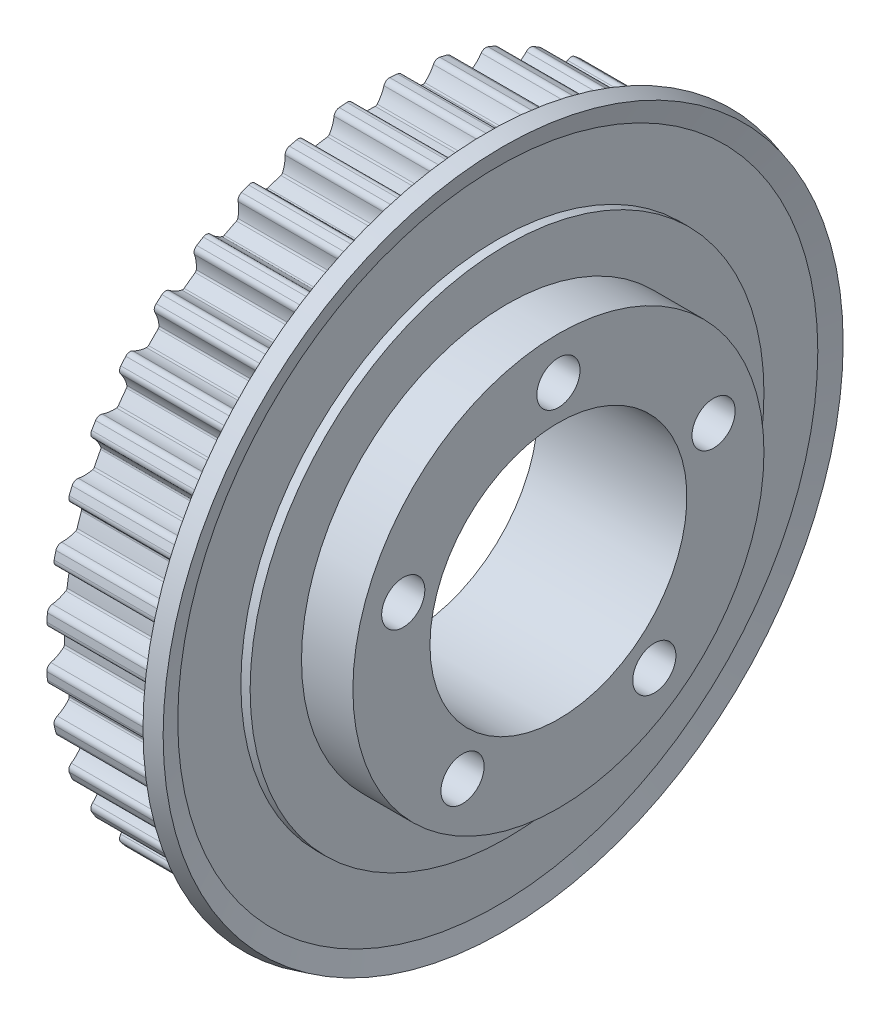
SolidWorks part; units mm, degrees
ref_plane "Front Plane" through (0, 0, 0) normal (0, 0, 1) x (1, 0, 0)
ref_plane "Top Plane" through (0, 0, 0) normal (0, 1, 0) x (1, 0, 0)
ref_plane "Right Plane" through (0, 0, 0) normal (1, 0, 0) x (0, 0, -1)
ref_plane "Plane1" through (0, 0, 0) normal (0, 0, 1) x (1, 0, 0)
sketch "Sketch1" plane through (0, 0, 0) normal (0, 0, 1) x (1, 0, 0)
  line L0 (0, 0) -> (0, 25)
  line L1 (0, 25) -> (0.9, 25)
  line L2 (0.9, 25) -> (0.9, 31.1394)
  line L3 (0.9, 31.1394) -> (0.3784, 33.0859)
  line L4 (0.3784, 33.0859) -> (1.9239, 33.5)
  line L5 (1.9239, 33.5) -> (2.5, 31.35)
  line L6 (2.5, 31.35) -> (13.5, 31.35)
  line L7 (13.5, 31.35) -> (14.0761, 33.5)
  line L8 (14.0761, 33.5) -> (15.6216, 33.0859)
  line L9 (15.6216, 33.0859) -> (15.1, 31.1394)
  line L10 (15.1, 31.1394) -> (15.1, 25)
  line L11 (15.1, 25) -> (16, 25)
  line L12 (16, 25) -> (16, 23.5)
  line L13 (16, 23.5) -> (21, 23.5)
  line L14 (21, 23.5) -> (21, 0)
  line L15 (21, 0) -> (0, 0)
  line L16 (21, 0) -> (0, 0) construction
revolve "Revolve1" add sketch "Sketch1" angle 360 about L16 reverse direction yes
ref_plane "Plane2" through (0, 0, 0) normal (0, 0, 1) x (1, 0, 0)
sketch "Sketch2" plane through (0, 0, 0) normal (0, 0, 1) x (1, 0, 0)
  line L0 (0, 0) -> (0, 12.5)
  line L1 (0, 12.5) -> (21, 12.5)
  line L2 (21, 12.5) -> (21, 0)
  line L3 (21, 0) -> (0, 0)
  line L4 (21, 0) -> (0, 0) construction
revolve "Cut-Revolve1" cut sketch "Sketch2" angle 360 about L4 reverse direction yes
ref_plane "Plane3" through (2.5, 0, 0) normal (1, 0, 0) x (0, 0, -1)
sketch "Sketch3" plane through (2.5, 0, 0) normal (1, 0, 0) x (0, 0, -1)
  line L0 (2.0877, 31.2804) -> (2.0877, 31.7615)
  line L1 (-2.0877, 31.7615) -> (-2.0877, 31.2804)
  arc A0 (-2.0877, 31.2804) -> (-1.5225, 30.8836) centre (-2.0511, 30.7316) cw
  arc A1 (-1.5225, 30.8836) -> (-0.8639, 29.6599) centre (1.625, 31.7885) ccw
  arc A2 (-0.8639, 29.6599) -> (-0.6683, 29.5725) centre (-0.6739, 29.8224) ccw
  arc A3 (-0.6683, 29.5725) -> (0.6683, 29.5725) centre (0, 0) cw
  arc A4 (0.6683, 29.5725) -> (0.8639, 29.6599) centre (0.6739, 29.8224) ccw
  arc A5 (0.8639, 29.6599) -> (1.5225, 30.8836) centre (-1.625, 31.7885) ccw
  arc A6 (1.5225, 30.8836) -> (2.0877, 31.2804) centre (2.0511, 30.7316) cw
  arc A7 (2.0877, 31.7615) -> (-2.0877, 31.7615) centre (0, 0) ccw
extrude "Cut-Extrude1" cut sketch "Sketch3" along normal blind 11
ref_plane "Plane4" through (2.5, 0, 0) normal (1, 0, 0) x (0, 0, -1)
sketch "Sketch4" plane through (2.5, 0, 0) normal (1, 0, 0) x (0, 0, -1)
  line L0 (6.9554, 30.5687) -> (7.0306, 31.0438)
  line L1 (2.9066, 31.697) -> (2.8313, 31.2219)
  arc A0 (2.8313, 31.2219) -> (3.3275, 30.7415) centre (2.7816, 30.6741) cw
  arc A1 (3.3275, 30.7415) -> (3.7865, 29.4299) centre (6.5778, 31.1429) ccw
  arc A2 (3.7865, 29.4299) -> (3.9661, 29.3129) centre (3.9996, 29.5606) ccw
  arc A3 (3.9661, 29.3129) -> (5.2862, 29.1038) centre (0, 0) cw
  arc A4 (5.2862, 29.1038) -> (5.4931, 29.1596) centre (5.3309, 29.3498) ccw
  arc A5 (5.4931, 29.1596) -> (6.335, 30.2652) centre (3.3678, 31.6513) ccw
  arc A6 (6.335, 30.2652) -> (6.9554, 30.5687) centre (6.8333, 30.0324) cw
  arc A7 (7.0306, 31.0438) -> (2.9066, 31.697) centre (0, 0) ccw
extrude "Cut-Extrude2" cut sketch "Sketch4" along normal blind 11
ref_plane "Plane5" through (2.5, 0, 0) normal (1, 0, 0) x (0, 0, -1)
sketch "Sketch5" plane through (2.5, 0, 0) normal (1, 0, 0) x (0, 0, -1)
  line L0 (11.6517, 29.1043) -> (11.8004, 29.5618)
  line L1 (7.8293, 30.8521) -> (7.6806, 30.3946)
  arc A0 (7.6806, 30.3946) -> (8.0956, 29.8425) centre (7.5459, 29.8613) cw
  arc A1 (8.0956, 29.8425) -> (8.3438, 28.4752) centre (11.3687, 29.7305) ccw
  arc A2 (8.3438, 28.4752) -> (8.5028, 28.3316) centre (8.5747, 28.571) ccw
  arc A3 (8.5028, 28.3316) -> (9.774, 27.9186) centre (0, 0) cw
  arc A4 (9.774, 27.9186) -> (9.987, 27.9413) centre (9.8566, 28.1545) ccw
  arc A5 (9.987, 27.9413) -> (10.9915, 28.9016) centre (8.2777, 30.7348) ccw
  arc A6 (10.9915, 28.9016) -> (11.6517, 29.1043) centre (11.4473, 28.5937) cw
  arc A7 (11.8004, 29.5618) -> (7.8293, 30.8521) centre (0, 0) ccw
extrude "Cut-Extrude3" cut sketch "Sketch5" along normal blind 11
ref_plane "Plane6" through (2.5, 0, 0) normal (1, 0, 0) x (0, 0, -1)
sketch "Sketch6" plane through (2.5, 0, 0) normal (1, 0, 0) x (0, 0, -1)
  line L0 (16.0612, 26.9232) -> (16.2796, 27.3519)
  line L1 (12.5592, 29.2475) -> (12.3408, 28.8189)
  arc A0 (12.3408, 28.8189) -> (12.6643, 28.2087) centre (12.1243, 28.3133) cw
  arc A1 (12.6643, 28.2087) -> (12.6956, 26.8194) centre (15.8796, 27.586) ccw
  arc A2 (12.6956, 26.8194) -> (12.8302, 26.6526) centre (12.9386, 26.8779) ccw
  arc A3 (12.8302, 26.6526) -> (14.021, 26.0459) centre (0, 0) cw
  arc A4 (14.021, 26.0459) -> (14.2351, 26.035) centre (14.1396, 26.266) ccw
  arc A5 (14.2351, 26.035) -> (15.3774, 26.8263) centre (12.9838, 29.0615) ccw
  arc A6 (15.3774, 26.8263) -> (16.0612, 26.9232) centre (15.7794, 26.4509) cw
  arc A7 (16.2796, 27.3519) -> (12.5592, 29.2475) centre (0, 0) ccw
extrude "Cut-Extrude4" cut sketch "Sketch6" along normal blind 11
ref_plane "Plane7" through (2.5, 0, 0) normal (1, 0, 0) x (0, 0, -1)
sketch "Sketch7" plane through (2.5, 0, 0) normal (1, 0, 0) x (0, 0, -1)
  line L0 (20.0752, 24.0793) -> (20.3579, 24.4684)
  line L1 (16.9799, 26.9227) -> (16.6972, 26.5335)
  arc A0 (16.6972, 26.5335) -> (16.9212, 25.8803) centre (16.4042, 26.068) cw
  arc A1 (16.9212, 25.8803) -> (16.7347, 24.5032) centre (19.9995, 24.7623) ccw
  arc A2 (16.7347, 24.5032) -> (16.8416, 24.3174) centre (16.9839, 24.5229) ccw
  arc A3 (16.8416, 24.3174) -> (17.9229, 23.5318) centre (0, 0) cw
  arc A4 (17.9229, 23.5318) -> (18.1326, 23.4876) centre (18.0744, 23.7307) ccw
  arc A5 (18.1326, 23.4876) -> (19.3847, 24.0904) centre (17.3702, 26.6726) ccw
  arc A6 (19.3847, 24.0904) -> (20.0752, 24.0793) centre (19.723, 23.6568) cw
  arc A7 (20.3579, 24.4684) -> (16.9799, 26.9227) centre (0, 0) ccw
extrude "Cut-Extrude5" cut sketch "Sketch7" along normal blind 11
ref_plane "Plane8" through (2.5, 0, 0) normal (1, 0, 0) x (0, 0, -1)
sketch "Sketch8" plane through (2.5, 0, 0) normal (1, 0, 0) x (0, 0, -1)
  line L0 (23.5948, 20.6423) -> (23.935, 20.9825)
  line L1 (20.9825, 23.935) -> (20.6423, 23.5948)
  arc A0 (20.6423, 23.5948) -> (20.7614, 22.9146) centre (20.2802, 23.1809) cw
  arc A1 (20.7614, 22.9146) -> (20.3618, 21.5836) centre (23.6269, 21.3288) ccw
  arc A2 (20.3618, 21.5836) -> (20.4383, 21.3834) centre (20.6111, 21.5641) ccw
  arc A3 (20.4383, 21.3834) -> (21.3834, 20.4383) centre (0, 0) cw
  arc A4 (21.3834, 20.4383) -> (21.5836, 20.3618) centre (21.5641, 20.6111) ccw
  arc A5 (21.5836, 20.3618) -> (22.9146, 20.7614) centre (21.3288, 23.6269) ccw
  arc A6 (22.9146, 20.7614) -> (23.5948, 20.6423) centre (23.1809, 20.2802) cw
  arc A7 (23.935, 20.9825) -> (20.9825, 23.935) centre (0, 0) ccw
extrude "Cut-Extrude6" cut sketch "Sketch8" along normal blind 11
ref_plane "Plane9" through (2.5, 0, 0) normal (1, 0, 0) x (0, 0, -1)
sketch "Sketch9" plane through (2.5, 0, 0) normal (1, 0, 0) x (0, 0, -1)
  line L0 (26.5335, 16.6972) -> (26.9227, 16.9799)
  line L1 (24.4684, 20.3579) -> (24.0793, 20.0752)
  arc A0 (24.0793, 20.0752) -> (24.0904, 19.3847) centre (23.6568, 19.723) cw
  arc A1 (24.0904, 19.3847) -> (23.4876, 18.1326) centre (26.6726, 17.3702) ccw
  arc A2 (23.4876, 18.1326) -> (23.5318, 17.9229) centre (23.7307, 18.0744) ccw
  arc A3 (23.5318, 17.9229) -> (24.3174, 16.8416) centre (0, 0) cw
  arc A4 (24.3174, 16.8416) -> (24.5032, 16.7347) centre (24.5229, 16.9839) ccw
  arc A5 (24.5032, 16.7347) -> (25.8803, 16.9212) centre (24.7623, 19.9995) ccw
  arc A6 (25.8803, 16.9212) -> (26.5335, 16.6972) centre (26.068, 16.4042) cw
  arc A7 (26.9227, 16.9799) -> (24.4684, 20.3579) centre (0, 0) ccw
extrude "Cut-Extrude7" cut sketch "Sketch9" along normal blind 11
ref_plane "Plane10" through (2.5, 0, 0) normal (1, 0, 0) x (0, 0, -1)
sketch "Sketch10" plane through (2.5, 0, 0) normal (1, 0, 0) x (0, 0, -1)
  line L0 (28.8189, 12.3408) -> (29.2475, 12.5592)
  line L1 (27.3519, 16.2796) -> (26.9232, 16.0612)
  arc A0 (26.9232, 16.0612) -> (26.8263, 15.3774) centre (26.4509, 15.7794) cw
  arc A1 (26.8263, 15.3774) -> (26.035, 14.2351) centre (29.0615, 12.9838) ccw
  arc A2 (26.035, 14.2351) -> (26.0459, 14.021) centre (26.266, 14.1396) ccw
  arc A3 (26.0459, 14.021) -> (26.6526, 12.8302) centre (0, 0) cw
  arc A4 (26.6526, 12.8302) -> (26.8194, 12.6956) centre (26.8779, 12.9386) ccw
  arc A5 (26.8194, 12.6956) -> (28.2087, 12.6643) centre (27.586, 15.8796) ccw
  arc A6 (28.2087, 12.6643) -> (28.8189, 12.3408) centre (28.3133, 12.1243) cw
  arc A7 (29.2475, 12.5592) -> (27.3519, 16.2796) centre (0, 0) ccw
extrude "Cut-Extrude8" cut sketch "Sketch10" along normal blind 11
ref_plane "Plane11" through (2.5, 0, 0) normal (1, 0, 0) x (0, 0, -1)
sketch "Sketch11" plane through (2.5, 0, 0) normal (1, 0, 0) x (0, 0, -1)
  line L0 (30.3946, 7.6806) -> (30.8521, 7.8293)
  line L1 (29.5618, 11.8004) -> (29.1043, 11.6517)
  arc A0 (29.1043, 11.6517) -> (28.9016, 10.9915) centre (28.5937, 11.4473) cw
  arc A1 (28.9016, 10.9915) -> (27.9413, 9.987) centre (30.7348, 8.2777) ccw
  arc A2 (27.9413, 9.987) -> (27.9186, 9.774) centre (28.1545, 9.8566) ccw
  arc A3 (27.9186, 9.774) -> (28.3316, 8.5028) centre (0, 0) cw
  arc A4 (28.3316, 8.5028) -> (28.4752, 8.3438) centre (28.571, 8.5747) ccw
  arc A5 (28.4752, 8.3438) -> (29.8425, 8.0956) centre (29.7305, 11.3687) ccw
  arc A6 (29.8425, 8.0956) -> (30.3946, 7.6806) centre (29.8613, 7.5459) cw
  arc A7 (30.8521, 7.8293) -> (29.5618, 11.8004) centre (0, 0) ccw
extrude "Cut-Extrude9" cut sketch "Sketch11" along normal blind 11
ref_plane "Plane12" through (2.5, 0, 0) normal (1, 0, 0) x (0, 0, -1)
sketch "Sketch12" plane through (2.5, 0, 0) normal (1, 0, 0) x (0, 0, -1)
  line L0 (31.2219, 2.8313) -> (31.697, 2.9066)
  line L1 (31.0438, 7.0306) -> (30.5687, 6.9554)
  arc A0 (30.5687, 6.9554) -> (30.2652, 6.335) centre (30.0324, 6.8333) cw
  arc A1 (30.2652, 6.335) -> (29.1596, 5.4931) centre (31.6513, 3.3678) ccw
  arc A2 (29.1596, 5.4931) -> (29.1038, 5.2862) centre (29.3498, 5.3309) ccw
  arc A3 (29.1038, 5.2862) -> (29.3129, 3.9661) centre (0, 0) cw
  arc A4 (29.3129, 3.9661) -> (29.4299, 3.7865) centre (29.5606, 3.9996) ccw
  arc A5 (29.4299, 3.7865) -> (30.7415, 3.3275) centre (31.1429, 6.5778) ccw
  arc A6 (30.7415, 3.3275) -> (31.2219, 2.8313) centre (30.6741, 2.7816) cw
  arc A7 (31.697, 2.9066) -> (31.0438, 7.0306) centre (0, 0) ccw
extrude "Cut-Extrude10" cut sketch "Sketch12" along normal blind 11
ref_plane "Plane13" through (2.5, 0, 0) normal (1, 0, 0) x (0, 0, -1)
sketch "Sketch13" plane through (2.5, 0, 0) normal (1, 0, 0) x (0, 0, -1)
  line L0 (31.2804, -2.0877) -> (31.7615, -2.0877)
  line L1 (31.7615, 2.0877) -> (31.2804, 2.0877)
  arc A0 (31.2804, 2.0877) -> (30.8836, 1.5225) centre (30.7316, 2.0511) cw
  arc A1 (30.8836, 1.5225) -> (29.6599, 0.8639) centre (31.7885, -1.625) ccw
  arc A2 (29.6599, 0.8639) -> (29.5725, 0.6683) centre (29.8224, 0.6739) ccw
  arc A3 (29.5725, 0.6683) -> (29.5725, -0.6683) centre (0, 0) cw
  arc A4 (29.5725, -0.6683) -> (29.6599, -0.8639) centre (29.8224, -0.6739) ccw
  arc A5 (29.6599, -0.8639) -> (30.8836, -1.5225) centre (31.7885, 1.625) ccw
  arc A6 (30.8836, -1.5225) -> (31.2804, -2.0877) centre (30.7316, -2.0511) cw
  arc A7 (31.7615, -2.0877) -> (31.7615, 2.0877) centre (0, 0) ccw
extrude "Cut-Extrude11" cut sketch "Sketch13" along normal blind 11
ref_plane "Plane14" through (2.5, 0, 0) normal (1, 0, 0) x (0, 0, -1)
sketch "Sketch14" plane through (2.5, 0, 0) normal (1, 0, 0) x (0, 0, -1)
  line L0 (30.5687, -6.9554) -> (31.0438, -7.0306)
  line L1 (31.697, -2.9066) -> (31.2219, -2.8313)
  arc A0 (31.2219, -2.8313) -> (30.7415, -3.3275) centre (30.6741, -2.7816) cw
  arc A1 (30.7415, -3.3275) -> (29.4299, -3.7865) centre (31.1429, -6.5778) ccw
  arc A2 (29.4299, -3.7865) -> (29.3129, -3.9661) centre (29.5606, -3.9996) ccw
  arc A3 (29.3129, -3.9661) -> (29.1038, -5.2862) centre (0, 0) cw
  arc A4 (29.1038, -5.2862) -> (29.1596, -5.4931) centre (29.3498, -5.3309) ccw
  arc A5 (29.1596, -5.4931) -> (30.2652, -6.335) centre (31.6513, -3.3678) ccw
  arc A6 (30.2652, -6.335) -> (30.5687, -6.9554) centre (30.0324, -6.8333) cw
  arc A7 (31.0438, -7.0306) -> (31.697, -2.9066) centre (0, 0) ccw
extrude "Cut-Extrude12" cut sketch "Sketch14" along normal blind 11
ref_plane "Plane15" through (2.5, 0, 0) normal (1, 0, 0) x (0, 0, -1)
sketch "Sketch15" plane through (2.5, 0, 0) normal (1, 0, 0) x (0, 0, -1)
  line L0 (29.1043, -11.6517) -> (29.5618, -11.8004)
  line L1 (30.8521, -7.8293) -> (30.3946, -7.6806)
  arc A0 (30.3946, -7.6806) -> (29.8425, -8.0956) centre (29.8613, -7.5459) cw
  arc A1 (29.8425, -8.0956) -> (28.4752, -8.3438) centre (29.7305, -11.3687) ccw
  arc A2 (28.4752, -8.3438) -> (28.3316, -8.5028) centre (28.571, -8.5747) ccw
  arc A3 (28.3316, -8.5028) -> (27.9186, -9.774) centre (0, 0) cw
  arc A4 (27.9186, -9.774) -> (27.9413, -9.987) centre (28.1545, -9.8566) ccw
  arc A5 (27.9413, -9.987) -> (28.9016, -10.9915) centre (30.7348, -8.2777) ccw
  arc A6 (28.9016, -10.9915) -> (29.1043, -11.6517) centre (28.5937, -11.4473) cw
  arc A7 (29.5618, -11.8004) -> (30.8521, -7.8293) centre (0, 0) ccw
extrude "Cut-Extrude13" cut sketch "Sketch15" along normal blind 11
ref_plane "Plane16" through (2.5, 0, 0) normal (1, 0, 0) x (0, 0, -1)
sketch "Sketch16" plane through (2.5, 0, 0) normal (1, 0, 0) x (0, 0, -1)
  line L0 (26.9232, -16.0612) -> (27.3519, -16.2796)
  line L1 (29.2475, -12.5592) -> (28.8189, -12.3408)
  arc A0 (28.8189, -12.3408) -> (28.2087, -12.6643) centre (28.3133, -12.1243) cw
  arc A1 (28.2087, -12.6643) -> (26.8194, -12.6956) centre (27.586, -15.8796) ccw
  arc A2 (26.8194, -12.6956) -> (26.6526, -12.8302) centre (26.8779, -12.9386) ccw
  arc A3 (26.6526, -12.8302) -> (26.0459, -14.021) centre (0, 0) cw
  arc A4 (26.0459, -14.021) -> (26.035, -14.2351) centre (26.266, -14.1396) ccw
  arc A5 (26.035, -14.2351) -> (26.8263, -15.3774) centre (29.0615, -12.9838) ccw
  arc A6 (26.8263, -15.3774) -> (26.9232, -16.0612) centre (26.4509, -15.7794) cw
  arc A7 (27.3519, -16.2796) -> (29.2475, -12.5592) centre (0, 0) ccw
extrude "Cut-Extrude14" cut sketch "Sketch16" along normal blind 11
ref_plane "Plane17" through (2.5, 0, 0) normal (1, 0, 0) x (0, 0, -1)
sketch "Sketch17" plane through (2.5, 0, 0) normal (1, 0, 0) x (0, 0, -1)
  line L0 (24.0793, -20.0752) -> (24.4684, -20.3579)
  line L1 (26.9227, -16.9799) -> (26.5335, -16.6972)
  arc A0 (26.5335, -16.6972) -> (25.8803, -16.9212) centre (26.068, -16.4042) cw
  arc A1 (25.8803, -16.9212) -> (24.5032, -16.7347) centre (24.7623, -19.9995) ccw
  arc A2 (24.5032, -16.7347) -> (24.3174, -16.8416) centre (24.5229, -16.9839) ccw
  arc A3 (24.3174, -16.8416) -> (23.5318, -17.9229) centre (0, 0) cw
  arc A4 (23.5318, -17.9229) -> (23.4876, -18.1326) centre (23.7307, -18.0744) ccw
  arc A5 (23.4876, -18.1326) -> (24.0904, -19.3847) centre (26.6726, -17.3702) ccw
  arc A6 (24.0904, -19.3847) -> (24.0793, -20.0752) centre (23.6568, -19.723) cw
  arc A7 (24.4684, -20.3579) -> (26.9227, -16.9799) centre (0, 0) ccw
extrude "Cut-Extrude15" cut sketch "Sketch17" along normal blind 11
ref_plane "Plane18" through (2.5, 0, 0) normal (1, 0, 0) x (0, 0, -1)
sketch "Sketch18" plane through (2.5, 0, 0) normal (1, 0, 0) x (0, 0, -1)
  line L0 (20.6423, -23.5948) -> (20.9825, -23.935)
  line L1 (23.935, -20.9825) -> (23.5948, -20.6423)
  arc A0 (23.5948, -20.6423) -> (22.9146, -20.7614) centre (23.1809, -20.2802) cw
  arc A1 (22.9146, -20.7614) -> (21.5836, -20.3618) centre (21.3288, -23.6269) ccw
  arc A2 (21.5836, -20.3618) -> (21.3834, -20.4383) centre (21.5641, -20.6111) ccw
  arc A3 (21.3834, -20.4383) -> (20.4383, -21.3834) centre (0, 0) cw
  arc A4 (20.4383, -21.3834) -> (20.3618, -21.5836) centre (20.6111, -21.5641) ccw
  arc A5 (20.3618, -21.5836) -> (20.7614, -22.9146) centre (23.6269, -21.3288) ccw
  arc A6 (20.7614, -22.9146) -> (20.6423, -23.5948) centre (20.2802, -23.1809) cw
  arc A7 (20.9825, -23.935) -> (23.935, -20.9825) centre (0, 0) ccw
extrude "Cut-Extrude16" cut sketch "Sketch18" along normal blind 11
ref_plane "Plane19" through (2.5, 0, 0) normal (1, 0, 0) x (0, 0, -1)
sketch "Sketch19" plane through (2.5, 0, 0) normal (1, 0, 0) x (0, 0, -1)
  line L0 (16.6972, -26.5335) -> (16.9799, -26.9227)
  line L1 (20.3579, -24.4684) -> (20.0752, -24.0793)
  arc A0 (20.0752, -24.0793) -> (19.3847, -24.0904) centre (19.723, -23.6568) cw
  arc A1 (19.3847, -24.0904) -> (18.1326, -23.4876) centre (17.3702, -26.6726) ccw
  arc A2 (18.1326, -23.4876) -> (17.9229, -23.5318) centre (18.0744, -23.7307) ccw
  arc A3 (17.9229, -23.5318) -> (16.8416, -24.3174) centre (0, 0) cw
  arc A4 (16.8416, -24.3174) -> (16.7347, -24.5032) centre (16.9839, -24.5229) ccw
  arc A5 (16.7347, -24.5032) -> (16.9212, -25.8803) centre (19.9995, -24.7623) ccw
  arc A6 (16.9212, -25.8803) -> (16.6972, -26.5335) centre (16.4042, -26.068) cw
  arc A7 (16.9799, -26.9227) -> (20.3579, -24.4684) centre (0, 0) ccw
extrude "Cut-Extrude17" cut sketch "Sketch19" along normal blind 11
ref_plane "Plane20" through (2.5, 0, 0) normal (1, 0, 0) x (0, 0, -1)
sketch "Sketch20" plane through (2.5, 0, 0) normal (1, 0, 0) x (0, 0, -1)
  line L0 (12.3408, -28.8189) -> (12.5592, -29.2475)
  line L1 (16.2796, -27.3519) -> (16.0612, -26.9232)
  arc A0 (16.0612, -26.9232) -> (15.3774, -26.8263) centre (15.7794, -26.4509) cw
  arc A1 (15.3774, -26.8263) -> (14.2351, -26.035) centre (12.9838, -29.0615) ccw
  arc A2 (14.2351, -26.035) -> (14.021, -26.0459) centre (14.1396, -26.266) ccw
  arc A3 (14.021, -26.0459) -> (12.8302, -26.6526) centre (0, 0) cw
  arc A4 (12.8302, -26.6526) -> (12.6956, -26.8194) centre (12.9386, -26.8779) ccw
  arc A5 (12.6956, -26.8194) -> (12.6643, -28.2087) centre (15.8796, -27.586) ccw
  arc A6 (12.6643, -28.2087) -> (12.3408, -28.8189) centre (12.1243, -28.3133) cw
  arc A7 (12.5592, -29.2475) -> (16.2796, -27.3519) centre (0, 0) ccw
extrude "Cut-Extrude18" cut sketch "Sketch20" along normal blind 11
ref_plane "Plane21" through (2.5, 0, 0) normal (1, 0, 0) x (0, 0, -1)
sketch "Sketch21" plane through (2.5, 0, 0) normal (1, 0, 0) x (0, 0, -1)
  line L0 (7.6806, -30.3946) -> (7.8293, -30.8521)
  line L1 (11.8004, -29.5618) -> (11.6517, -29.1043)
  arc A0 (11.6517, -29.1043) -> (10.9915, -28.9016) centre (11.4473, -28.5937) cw
  arc A1 (10.9915, -28.9016) -> (9.987, -27.9413) centre (8.2777, -30.7348) ccw
  arc A2 (9.987, -27.9413) -> (9.774, -27.9186) centre (9.8566, -28.1545) ccw
  arc A3 (9.774, -27.9186) -> (8.5028, -28.3316) centre (0, 0) cw
  arc A4 (8.5028, -28.3316) -> (8.3438, -28.4752) centre (8.5747, -28.571) ccw
  arc A5 (8.3438, -28.4752) -> (8.0956, -29.8425) centre (11.3687, -29.7305) ccw
  arc A6 (8.0956, -29.8425) -> (7.6806, -30.3946) centre (7.5459, -29.8613) cw
  arc A7 (7.8293, -30.8521) -> (11.8004, -29.5618) centre (0, 0) ccw
extrude "Cut-Extrude19" cut sketch "Sketch21" along normal blind 11
ref_plane "Plane22" through (2.5, 0, 0) normal (1, 0, 0) x (0, 0, -1)
sketch "Sketch22" plane through (2.5, 0, 0) normal (1, 0, 0) x (0, 0, -1)
  line L0 (2.8313, -31.2219) -> (2.9066, -31.697)
  line L1 (7.0306, -31.0438) -> (6.9554, -30.5687)
  arc A0 (6.9554, -30.5687) -> (6.335, -30.2652) centre (6.8333, -30.0324) cw
  arc A1 (6.335, -30.2652) -> (5.4931, -29.1596) centre (3.3678, -31.6513) ccw
  arc A2 (5.4931, -29.1596) -> (5.2862, -29.1038) centre (5.3309, -29.3498) ccw
  arc A3 (5.2862, -29.1038) -> (3.9661, -29.3129) centre (0, 0) cw
  arc A4 (3.9661, -29.3129) -> (3.7865, -29.4299) centre (3.9996, -29.5606) ccw
  arc A5 (3.7865, -29.4299) -> (3.3275, -30.7415) centre (6.5778, -31.1429) ccw
  arc A6 (3.3275, -30.7415) -> (2.8313, -31.2219) centre (2.7816, -30.6741) cw
  arc A7 (2.9066, -31.697) -> (7.0306, -31.0438) centre (0, 0) ccw
extrude "Cut-Extrude20" cut sketch "Sketch22" along normal blind 11
ref_plane "Plane23" through (2.5, 0, 0) normal (1, 0, 0) x (0, 0, -1)
sketch "Sketch23" plane through (2.5, 0, 0) normal (1, 0, 0) x (0, 0, -1)
  line L0 (-2.0877, -31.2804) -> (-2.0877, -31.7615)
  line L1 (2.0877, -31.7615) -> (2.0877, -31.2804)
  arc A0 (2.0877, -31.2804) -> (1.5225, -30.8836) centre (2.0511, -30.7316) cw
  arc A1 (1.5225, -30.8836) -> (0.8639, -29.6599) centre (-1.625, -31.7885) ccw
  arc A2 (0.8639, -29.6599) -> (0.6683, -29.5725) centre (0.6739, -29.8224) ccw
  arc A3 (0.6683, -29.5725) -> (-0.6683, -29.5725) centre (0, 0) cw
  arc A4 (-0.6683, -29.5725) -> (-0.8639, -29.6599) centre (-0.6739, -29.8224) ccw
  arc A5 (-0.8639, -29.6599) -> (-1.5225, -30.8836) centre (1.625, -31.7885) ccw
  arc A6 (-1.5225, -30.8836) -> (-2.0877, -31.2804) centre (-2.0511, -30.7316) cw
  arc A7 (-2.0877, -31.7615) -> (2.0877, -31.7615) centre (0, 0) ccw
extrude "Cut-Extrude21" cut sketch "Sketch23" along normal blind 11
ref_plane "Plane24" through (2.5, 0, 0) normal (1, 0, 0) x (0, 0, -1)
sketch "Sketch24" plane through (2.5, 0, 0) normal (1, 0, 0) x (0, 0, -1)
  line L0 (-6.9554, -30.5687) -> (-7.0306, -31.0438)
  line L1 (-2.9066, -31.697) -> (-2.8313, -31.2219)
  arc A0 (-2.8313, -31.2219) -> (-3.3275, -30.7415) centre (-2.7816, -30.6741) cw
  arc A1 (-3.3275, -30.7415) -> (-3.7865, -29.4299) centre (-6.5778, -31.1429) ccw
  arc A2 (-3.7865, -29.4299) -> (-3.9661, -29.3129) centre (-3.9996, -29.5606) ccw
  arc A3 (-3.9661, -29.3129) -> (-5.2862, -29.1038) centre (0, 0) cw
  arc A4 (-5.2862, -29.1038) -> (-5.4931, -29.1596) centre (-5.3309, -29.3498) ccw
  arc A5 (-5.4931, -29.1596) -> (-6.335, -30.2652) centre (-3.3678, -31.6513) ccw
  arc A6 (-6.335, -30.2652) -> (-6.9554, -30.5687) centre (-6.8333, -30.0324) cw
  arc A7 (-7.0306, -31.0438) -> (-2.9066, -31.697) centre (0, 0) ccw
extrude "Cut-Extrude22" cut sketch "Sketch24" along normal blind 11
ref_plane "Plane25" through (2.5, 0, 0) normal (1, 0, 0) x (0, 0, -1)
sketch "Sketch25" plane through (2.5, 0, 0) normal (1, 0, 0) x (0, 0, -1)
  line L0 (-11.6517, -29.1043) -> (-11.8004, -29.5618)
  line L1 (-7.8293, -30.8521) -> (-7.6806, -30.3946)
  arc A0 (-7.6806, -30.3946) -> (-8.0956, -29.8425) centre (-7.5459, -29.8613) cw
  arc A1 (-8.0956, -29.8425) -> (-8.3438, -28.4752) centre (-11.3687, -29.7305) ccw
  arc A2 (-8.3438, -28.4752) -> (-8.5028, -28.3316) centre (-8.5747, -28.571) ccw
  arc A3 (-8.5028, -28.3316) -> (-9.774, -27.9186) centre (0, 0) cw
  arc A4 (-9.774, -27.9186) -> (-9.987, -27.9413) centre (-9.8566, -28.1545) ccw
  arc A5 (-9.987, -27.9413) -> (-10.9915, -28.9016) centre (-8.2777, -30.7348) ccw
  arc A6 (-10.9915, -28.9016) -> (-11.6517, -29.1043) centre (-11.4473, -28.5937) cw
  arc A7 (-11.8004, -29.5618) -> (-7.8293, -30.8521) centre (0, 0) ccw
extrude "Cut-Extrude23" cut sketch "Sketch25" along normal blind 11
ref_plane "Plane26" through (2.5, 0, 0) normal (1, 0, 0) x (0, 0, -1)
sketch "Sketch26" plane through (2.5, 0, 0) normal (1, 0, 0) x (0, 0, -1)
  line L0 (-16.0612, -26.9232) -> (-16.2796, -27.3519)
  line L1 (-12.5592, -29.2475) -> (-12.3408, -28.8189)
  arc A0 (-12.3408, -28.8189) -> (-12.6643, -28.2087) centre (-12.1243, -28.3133) cw
  arc A1 (-12.6643, -28.2087) -> (-12.6956, -26.8194) centre (-15.8796, -27.586) ccw
  arc A2 (-12.6956, -26.8194) -> (-12.8302, -26.6526) centre (-12.9386, -26.8779) ccw
  arc A3 (-12.8302, -26.6526) -> (-14.021, -26.0459) centre (0, 0) cw
  arc A4 (-14.021, -26.0459) -> (-14.2351, -26.035) centre (-14.1396, -26.266) ccw
  arc A5 (-14.2351, -26.035) -> (-15.3774, -26.8263) centre (-12.9838, -29.0615) ccw
  arc A6 (-15.3774, -26.8263) -> (-16.0612, -26.9232) centre (-15.7794, -26.4509) cw
  arc A7 (-16.2796, -27.3519) -> (-12.5592, -29.2475) centre (0, 0) ccw
extrude "Cut-Extrude24" cut sketch "Sketch26" along normal blind 11
ref_plane "Plane27" through (2.5, 0, 0) normal (1, 0, 0) x (0, 0, -1)
sketch "Sketch27" plane through (2.5, 0, 0) normal (1, 0, 0) x (0, 0, -1)
  line L0 (-20.0752, -24.0793) -> (-20.3579, -24.4684)
  line L1 (-16.9799, -26.9227) -> (-16.6972, -26.5335)
  arc A0 (-16.6972, -26.5335) -> (-16.9212, -25.8803) centre (-16.4042, -26.068) cw
  arc A1 (-16.9212, -25.8803) -> (-16.7347, -24.5032) centre (-19.9995, -24.7623) ccw
  arc A2 (-16.7347, -24.5032) -> (-16.8416, -24.3174) centre (-16.9839, -24.5229) ccw
  arc A3 (-16.8416, -24.3174) -> (-17.9229, -23.5318) centre (0, 0) cw
  arc A4 (-17.9229, -23.5318) -> (-18.1326, -23.4876) centre (-18.0744, -23.7307) ccw
  arc A5 (-18.1326, -23.4876) -> (-19.3847, -24.0904) centre (-17.3702, -26.6726) ccw
  arc A6 (-19.3847, -24.0904) -> (-20.0752, -24.0793) centre (-19.723, -23.6568) cw
  arc A7 (-20.3579, -24.4684) -> (-16.9799, -26.9227) centre (0, 0) ccw
extrude "Cut-Extrude25" cut sketch "Sketch27" along normal blind 11
ref_plane "Plane28" through (2.5, 0, 0) normal (1, 0, 0) x (0, 0, -1)
sketch "Sketch28" plane through (2.5, 0, 0) normal (1, 0, 0) x (0, 0, -1)
  line L0 (-23.5948, -20.6423) -> (-23.935, -20.9825)
  line L1 (-20.9825, -23.935) -> (-20.6423, -23.5948)
  arc A0 (-20.6423, -23.5948) -> (-20.7614, -22.9146) centre (-20.2802, -23.1809) cw
  arc A1 (-20.7614, -22.9146) -> (-20.3618, -21.5836) centre (-23.6269, -21.3288) ccw
  arc A2 (-20.3618, -21.5836) -> (-20.4383, -21.3834) centre (-20.6111, -21.5641) ccw
  arc A3 (-20.4383, -21.3834) -> (-21.3834, -20.4383) centre (0, 0) cw
  arc A4 (-21.3834, -20.4383) -> (-21.5836, -20.3618) centre (-21.5641, -20.6111) ccw
  arc A5 (-21.5836, -20.3618) -> (-22.9146, -20.7614) centre (-21.3288, -23.6269) ccw
  arc A6 (-22.9146, -20.7614) -> (-23.5948, -20.6423) centre (-23.1809, -20.2802) cw
  arc A7 (-23.935, -20.9825) -> (-20.9825, -23.935) centre (0, 0) ccw
extrude "Cut-Extrude26" cut sketch "Sketch28" along normal blind 11
ref_plane "Plane29" through (2.5, 0, 0) normal (1, 0, 0) x (0, 0, -1)
sketch "Sketch29" plane through (2.5, 0, 0) normal (1, 0, 0) x (0, 0, -1)
  line L0 (-26.5335, -16.6972) -> (-26.9227, -16.9799)
  line L1 (-24.4684, -20.3579) -> (-24.0793, -20.0752)
  arc A0 (-24.0793, -20.0752) -> (-24.0904, -19.3847) centre (-23.6568, -19.723) cw
  arc A1 (-24.0904, -19.3847) -> (-23.4876, -18.1326) centre (-26.6726, -17.3702) ccw
  arc A2 (-23.4876, -18.1326) -> (-23.5318, -17.9229) centre (-23.7307, -18.0744) ccw
  arc A3 (-23.5318, -17.9229) -> (-24.3174, -16.8416) centre (0, 0) cw
  arc A4 (-24.3174, -16.8416) -> (-24.5032, -16.7347) centre (-24.5229, -16.9839) ccw
  arc A5 (-24.5032, -16.7347) -> (-25.8803, -16.9212) centre (-24.7623, -19.9995) ccw
  arc A6 (-25.8803, -16.9212) -> (-26.5335, -16.6972) centre (-26.068, -16.4042) cw
  arc A7 (-26.9227, -16.9799) -> (-24.4684, -20.3579) centre (0, 0) ccw
extrude "Cut-Extrude27" cut sketch "Sketch29" along normal blind 11
ref_plane "Plane30" through (2.5, 0, 0) normal (1, 0, 0) x (0, 0, -1)
sketch "Sketch30" plane through (2.5, 0, 0) normal (1, 0, 0) x (0, 0, -1)
  line L0 (-28.8189, -12.3408) -> (-29.2475, -12.5592)
  line L1 (-27.3519, -16.2796) -> (-26.9232, -16.0612)
  arc A0 (-26.9232, -16.0612) -> (-26.8263, -15.3774) centre (-26.4509, -15.7794) cw
  arc A1 (-26.8263, -15.3774) -> (-26.035, -14.2351) centre (-29.0615, -12.9838) ccw
  arc A2 (-26.035, -14.2351) -> (-26.0459, -14.021) centre (-26.266, -14.1396) ccw
  arc A3 (-26.0459, -14.021) -> (-26.6526, -12.8302) centre (0, 0) cw
  arc A4 (-26.6526, -12.8302) -> (-26.8194, -12.6956) centre (-26.8779, -12.9386) ccw
  arc A5 (-26.8194, -12.6956) -> (-28.2087, -12.6643) centre (-27.586, -15.8796) ccw
  arc A6 (-28.2087, -12.6643) -> (-28.8189, -12.3408) centre (-28.3133, -12.1243) cw
  arc A7 (-29.2475, -12.5592) -> (-27.3519, -16.2796) centre (0, 0) ccw
extrude "Cut-Extrude28" cut sketch "Sketch30" along normal blind 11
ref_plane "Plane31" through (2.5, 0, 0) normal (1, 0, 0) x (0, 0, -1)
sketch "Sketch31" plane through (2.5, 0, 0) normal (1, 0, 0) x (0, 0, -1)
  line L0 (-30.3946, -7.6806) -> (-30.8521, -7.8293)
  line L1 (-29.5618, -11.8004) -> (-29.1043, -11.6517)
  arc A0 (-29.1043, -11.6517) -> (-28.9016, -10.9915) centre (-28.5937, -11.4473) cw
  arc A1 (-28.9016, -10.9915) -> (-27.9413, -9.987) centre (-30.7348, -8.2777) ccw
  arc A2 (-27.9413, -9.987) -> (-27.9186, -9.774) centre (-28.1545, -9.8566) ccw
  arc A3 (-27.9186, -9.774) -> (-28.3316, -8.5028) centre (0, 0) cw
  arc A4 (-28.3316, -8.5028) -> (-28.4752, -8.3438) centre (-28.571, -8.5747) ccw
  arc A5 (-28.4752, -8.3438) -> (-29.8425, -8.0956) centre (-29.7305, -11.3687) ccw
  arc A6 (-29.8425, -8.0956) -> (-30.3946, -7.6806) centre (-29.8613, -7.5459) cw
  arc A7 (-30.8521, -7.8293) -> (-29.5618, -11.8004) centre (0, 0) ccw
extrude "Cut-Extrude29" cut sketch "Sketch31" along normal blind 11
ref_plane "Plane32" through (2.5, 0, 0) normal (1, 0, 0) x (0, 0, -1)
sketch "Sketch32" plane through (2.5, 0, 0) normal (1, 0, 0) x (0, 0, -1)
  line L0 (-31.2219, -2.8313) -> (-31.697, -2.9066)
  line L1 (-31.0438, -7.0306) -> (-30.5687, -6.9554)
  arc A0 (-30.5687, -6.9554) -> (-30.2652, -6.335) centre (-30.0324, -6.8333) cw
  arc A1 (-30.2652, -6.335) -> (-29.1596, -5.4931) centre (-31.6513, -3.3678) ccw
  arc A2 (-29.1596, -5.4931) -> (-29.1038, -5.2862) centre (-29.3498, -5.3309) ccw
  arc A3 (-29.1038, -5.2862) -> (-29.3129, -3.9661) centre (0, 0) cw
  arc A4 (-29.3129, -3.9661) -> (-29.4299, -3.7865) centre (-29.5606, -3.9996) ccw
  arc A5 (-29.4299, -3.7865) -> (-30.7415, -3.3275) centre (-31.1429, -6.5778) ccw
  arc A6 (-30.7415, -3.3275) -> (-31.2219, -2.8313) centre (-30.6741, -2.7816) cw
  arc A7 (-31.697, -2.9066) -> (-31.0438, -7.0306) centre (0, 0) ccw
extrude "Cut-Extrude30" cut sketch "Sketch32" along normal blind 11
ref_plane "Plane33" through (2.5, 0, 0) normal (1, 0, 0) x (0, 0, -1)
sketch "Sketch33" plane through (2.5, 0, 0) normal (1, 0, 0) x (0, 0, -1)
  line L0 (-31.2804, 2.0877) -> (-31.7615, 2.0877)
  line L1 (-31.7615, -2.0877) -> (-31.2804, -2.0877)
  arc A0 (-31.2804, -2.0877) -> (-30.8836, -1.5225) centre (-30.7316, -2.0511) cw
  arc A1 (-30.8836, -1.5225) -> (-29.6599, -0.8639) centre (-31.7885, 1.625) ccw
  arc A2 (-29.6599, -0.8639) -> (-29.5725, -0.6683) centre (-29.8224, -0.6739) ccw
  arc A3 (-29.5725, -0.6683) -> (-29.5725, 0.6683) centre (0, 0) cw
  arc A4 (-29.5725, 0.6683) -> (-29.6599, 0.8639) centre (-29.8224, 0.6739) ccw
  arc A5 (-29.6599, 0.8639) -> (-30.8836, 1.5225) centre (-31.7885, -1.625) ccw
  arc A6 (-30.8836, 1.5225) -> (-31.2804, 2.0877) centre (-30.7316, 2.0511) cw
  arc A7 (-31.7615, 2.0877) -> (-31.7615, -2.0877) centre (0, 0) ccw
extrude "Cut-Extrude31" cut sketch "Sketch33" along normal blind 11
ref_plane "Plane34" through (2.5, 0, 0) normal (1, 0, 0) x (0, 0, -1)
sketch "Sketch34" plane through (2.5, 0, 0) normal (1, 0, 0) x (0, 0, -1)
  line L0 (-30.5687, 6.9554) -> (-31.0438, 7.0306)
  line L1 (-31.697, 2.9066) -> (-31.2219, 2.8313)
  arc A0 (-31.2219, 2.8313) -> (-30.7415, 3.3275) centre (-30.6741, 2.7816) cw
  arc A1 (-30.7415, 3.3275) -> (-29.4299, 3.7865) centre (-31.1429, 6.5778) ccw
  arc A2 (-29.4299, 3.7865) -> (-29.3129, 3.9661) centre (-29.5606, 3.9996) ccw
  arc A3 (-29.3129, 3.9661) -> (-29.1038, 5.2862) centre (0, 0) cw
  arc A4 (-29.1038, 5.2862) -> (-29.1596, 5.4931) centre (-29.3498, 5.3309) ccw
  arc A5 (-29.1596, 5.4931) -> (-30.2652, 6.335) centre (-31.6513, 3.3678) ccw
  arc A6 (-30.2652, 6.335) -> (-30.5687, 6.9554) centre (-30.0324, 6.8333) cw
  arc A7 (-31.0438, 7.0306) -> (-31.697, 2.9066) centre (0, 0) ccw
extrude "Cut-Extrude32" cut sketch "Sketch34" along normal blind 11
ref_plane "Plane35" through (2.5, 0, 0) normal (1, 0, 0) x (0, 0, -1)
sketch "Sketch35" plane through (2.5, 0, 0) normal (1, 0, 0) x (0, 0, -1)
  line L0 (-29.1043, 11.6517) -> (-29.5618, 11.8004)
  line L1 (-30.8521, 7.8293) -> (-30.3946, 7.6806)
  arc A0 (-30.3946, 7.6806) -> (-29.8425, 8.0956) centre (-29.8613, 7.5459) cw
  arc A1 (-29.8425, 8.0956) -> (-28.4752, 8.3438) centre (-29.7305, 11.3687) ccw
  arc A2 (-28.4752, 8.3438) -> (-28.3316, 8.5028) centre (-28.571, 8.5747) ccw
  arc A3 (-28.3316, 8.5028) -> (-27.9186, 9.774) centre (0, 0) cw
  arc A4 (-27.9186, 9.774) -> (-27.9413, 9.987) centre (-28.1545, 9.8566) ccw
  arc A5 (-27.9413, 9.987) -> (-28.9016, 10.9915) centre (-30.7348, 8.2777) ccw
  arc A6 (-28.9016, 10.9915) -> (-29.1043, 11.6517) centre (-28.5937, 11.4473) cw
  arc A7 (-29.5618, 11.8004) -> (-30.8521, 7.8293) centre (0, 0) ccw
extrude "Cut-Extrude33" cut sketch "Sketch35" along normal blind 11
ref_plane "Plane36" through (2.5, 0, 0) normal (1, 0, 0) x (0, 0, -1)
sketch "Sketch36" plane through (2.5, 0, 0) normal (1, 0, 0) x (0, 0, -1)
  line L0 (-26.9232, 16.0612) -> (-27.3519, 16.2796)
  line L1 (-29.2475, 12.5592) -> (-28.8189, 12.3408)
  arc A0 (-28.8189, 12.3408) -> (-28.2087, 12.6643) centre (-28.3133, 12.1243) cw
  arc A1 (-28.2087, 12.6643) -> (-26.8194, 12.6956) centre (-27.586, 15.8796) ccw
  arc A2 (-26.8194, 12.6956) -> (-26.6526, 12.8302) centre (-26.8779, 12.9386) ccw
  arc A3 (-26.6526, 12.8302) -> (-26.0459, 14.021) centre (0, 0) cw
  arc A4 (-26.0459, 14.021) -> (-26.035, 14.2351) centre (-26.266, 14.1396) ccw
  arc A5 (-26.035, 14.2351) -> (-26.8263, 15.3774) centre (-29.0615, 12.9838) ccw
  arc A6 (-26.8263, 15.3774) -> (-26.9232, 16.0612) centre (-26.4509, 15.7794) cw
  arc A7 (-27.3519, 16.2796) -> (-29.2475, 12.5592) centre (0, 0) ccw
extrude "Cut-Extrude34" cut sketch "Sketch36" along normal blind 11
ref_plane "Plane37" through (2.5, 0, 0) normal (1, 0, 0) x (0, 0, -1)
sketch "Sketch37" plane through (2.5, 0, 0) normal (1, 0, 0) x (0, 0, -1)
  line L0 (-24.0793, 20.0752) -> (-24.4684, 20.3579)
  line L1 (-26.9227, 16.9799) -> (-26.5335, 16.6972)
  arc A0 (-26.5335, 16.6972) -> (-25.8803, 16.9212) centre (-26.068, 16.4042) cw
  arc A1 (-25.8803, 16.9212) -> (-24.5032, 16.7347) centre (-24.7623, 19.9995) ccw
  arc A2 (-24.5032, 16.7347) -> (-24.3174, 16.8416) centre (-24.5229, 16.9839) ccw
  arc A3 (-24.3174, 16.8416) -> (-23.5318, 17.9229) centre (0, 0) cw
  arc A4 (-23.5318, 17.9229) -> (-23.4876, 18.1326) centre (-23.7307, 18.0744) ccw
  arc A5 (-23.4876, 18.1326) -> (-24.0904, 19.3847) centre (-26.6726, 17.3702) ccw
  arc A6 (-24.0904, 19.3847) -> (-24.0793, 20.0752) centre (-23.6568, 19.723) cw
  arc A7 (-24.4684, 20.3579) -> (-26.9227, 16.9799) centre (0, 0) ccw
extrude "Cut-Extrude35" cut sketch "Sketch37" along normal blind 11
ref_plane "Plane38" through (2.5, 0, 0) normal (1, 0, 0) x (0, 0, -1)
sketch "Sketch38" plane through (2.5, 0, 0) normal (1, 0, 0) x (0, 0, -1)
  line L0 (-20.6423, 23.5948) -> (-20.9825, 23.935)
  line L1 (-23.935, 20.9825) -> (-23.5948, 20.6423)
  arc A0 (-23.5948, 20.6423) -> (-22.9146, 20.7614) centre (-23.1809, 20.2802) cw
  arc A1 (-22.9146, 20.7614) -> (-21.5836, 20.3618) centre (-21.3288, 23.6269) ccw
  arc A2 (-21.5836, 20.3618) -> (-21.3834, 20.4383) centre (-21.5641, 20.6111) ccw
  arc A3 (-21.3834, 20.4383) -> (-20.4383, 21.3834) centre (0, 0) cw
  arc A4 (-20.4383, 21.3834) -> (-20.3618, 21.5836) centre (-20.6111, 21.5641) ccw
  arc A5 (-20.3618, 21.5836) -> (-20.7614, 22.9146) centre (-23.6269, 21.3288) ccw
  arc A6 (-20.7614, 22.9146) -> (-20.6423, 23.5948) centre (-20.2802, 23.1809) cw
  arc A7 (-20.9825, 23.935) -> (-23.935, 20.9825) centre (0, 0) ccw
extrude "Cut-Extrude36" cut sketch "Sketch38" along normal blind 11
ref_plane "Plane39" through (2.5, 0, 0) normal (1, 0, 0) x (0, 0, -1)
sketch "Sketch39" plane through (2.5, 0, 0) normal (1, 0, 0) x (0, 0, -1)
  line L0 (-16.6972, 26.5335) -> (-16.9799, 26.9227)
  line L1 (-20.3579, 24.4684) -> (-20.0752, 24.0793)
  arc A0 (-20.0752, 24.0793) -> (-19.3847, 24.0904) centre (-19.723, 23.6568) cw
  arc A1 (-19.3847, 24.0904) -> (-18.1326, 23.4876) centre (-17.3702, 26.6726) ccw
  arc A2 (-18.1326, 23.4876) -> (-17.9229, 23.5318) centre (-18.0744, 23.7307) ccw
  arc A3 (-17.9229, 23.5318) -> (-16.8416, 24.3174) centre (0, 0) cw
  arc A4 (-16.8416, 24.3174) -> (-16.7347, 24.5032) centre (-16.9839, 24.5229) ccw
  arc A5 (-16.7347, 24.5032) -> (-16.9212, 25.8803) centre (-19.9995, 24.7623) ccw
  arc A6 (-16.9212, 25.8803) -> (-16.6972, 26.5335) centre (-16.4042, 26.068) cw
  arc A7 (-16.9799, 26.9227) -> (-20.3579, 24.4684) centre (0, 0) ccw
extrude "Cut-Extrude37" cut sketch "Sketch39" along normal blind 11
ref_plane "Plane40" through (2.5, 0, 0) normal (1, 0, 0) x (0, 0, -1)
sketch "Sketch40" plane through (2.5, 0, 0) normal (1, 0, 0) x (0, 0, -1)
  line L0 (-12.3408, 28.8189) -> (-12.5592, 29.2475)
  line L1 (-16.2796, 27.3519) -> (-16.0612, 26.9232)
  arc A0 (-16.0612, 26.9232) -> (-15.3774, 26.8263) centre (-15.7794, 26.4509) cw
  arc A1 (-15.3774, 26.8263) -> (-14.2351, 26.035) centre (-12.9838, 29.0615) ccw
  arc A2 (-14.2351, 26.035) -> (-14.021, 26.0459) centre (-14.1396, 26.266) ccw
  arc A3 (-14.021, 26.0459) -> (-12.8302, 26.6526) centre (0, 0) cw
  arc A4 (-12.8302, 26.6526) -> (-12.6956, 26.8194) centre (-12.9386, 26.8779) ccw
  arc A5 (-12.6956, 26.8194) -> (-12.6643, 28.2087) centre (-15.8796, 27.586) ccw
  arc A6 (-12.6643, 28.2087) -> (-12.3408, 28.8189) centre (-12.1243, 28.3133) cw
  arc A7 (-12.5592, 29.2475) -> (-16.2796, 27.3519) centre (0, 0) ccw
extrude "Cut-Extrude38" cut sketch "Sketch40" along normal blind 11
ref_plane "Plane41" through (2.5, 0, 0) normal (1, 0, 0) x (0, 0, -1)
sketch "Sketch41" plane through (2.5, 0, 0) normal (1, 0, 0) x (0, 0, -1)
  line L0 (-7.6806, 30.3946) -> (-7.8293, 30.8521)
  line L1 (-11.8004, 29.5618) -> (-11.6517, 29.1043)
  arc A0 (-11.6517, 29.1043) -> (-10.9915, 28.9016) centre (-11.4473, 28.5937) cw
  arc A1 (-10.9915, 28.9016) -> (-9.987, 27.9413) centre (-8.2777, 30.7348) ccw
  arc A2 (-9.987, 27.9413) -> (-9.774, 27.9186) centre (-9.8566, 28.1545) ccw
  arc A3 (-9.774, 27.9186) -> (-8.5028, 28.3316) centre (0, 0) cw
  arc A4 (-8.5028, 28.3316) -> (-8.3438, 28.4752) centre (-8.5747, 28.571) ccw
  arc A5 (-8.3438, 28.4752) -> (-8.0956, 29.8425) centre (-11.3687, 29.7305) ccw
  arc A6 (-8.0956, 29.8425) -> (-7.6806, 30.3946) centre (-7.5459, 29.8613) cw
  arc A7 (-7.8293, 30.8521) -> (-11.8004, 29.5618) centre (0, 0) ccw
extrude "Cut-Extrude39" cut sketch "Sketch41" along normal blind 11
ref_plane "Plane42" through (2.5, 0, 0) normal (1, 0, 0) x (0, 0, -1)
sketch "Sketch42" plane through (2.5, 0, 0) normal (1, 0, 0) x (0, 0, -1)
  line L0 (-2.8313, 31.2219) -> (-2.9066, 31.697)
  line L1 (-7.0306, 31.0438) -> (-6.9554, 30.5687)
  arc A0 (-6.9554, 30.5687) -> (-6.335, 30.2652) centre (-6.8333, 30.0324) cw
  arc A1 (-6.335, 30.2652) -> (-5.4931, 29.1596) centre (-3.3678, 31.6513) ccw
  arc A2 (-5.4931, 29.1596) -> (-5.2862, 29.1038) centre (-5.3309, 29.3498) ccw
  arc A3 (-5.2862, 29.1038) -> (-3.9661, 29.3129) centre (0, 0) cw
  arc A4 (-3.9661, 29.3129) -> (-3.7865, 29.4299) centre (-3.9996, 29.5606) ccw
  arc A5 (-3.7865, 29.4299) -> (-3.3275, 30.7415) centre (-6.5778, 31.1429) ccw
  arc A6 (-3.3275, 30.7415) -> (-2.8313, 31.2219) centre (-2.7816, 30.6741) cw
  arc A7 (-2.9066, 31.697) -> (-7.0306, 31.0438) centre (0, 0) ccw
extrude "Cut-Extrude40" cut sketch "Sketch42" along normal blind 11
sketch "Sketch43" plane through (0, 0, 0) normal (0, 0, 1) x (1, 0, 0)
  line L0 (0, 0) -> (21, 0) construction
  line L1 (21, -23.5) -> (21, 23.5) construction
  line L2 (16, -25) -> (16, 25) construction
  line L3 (21, 23.5) -> (16, 23.5)
  line L4 (21, 23.5) -> (21, 20)
  line L5 (21, 20) -> (16, 20)
  line L6 (16, 23.5) -> (16, 20)
  dimension "D1" = 40
revolve "Cut-Revolve2" cut sketch "Sketch43" angle 360 about L0
hole_wizard "M5x0.8 Tapped Hole1" positions "Sketch45" profile "Sketch46" tap size "M5x0.8" standard "ANSI Metric" end condition through all
sketch "Sketch45" plane through (21, 0, 0) normal (1, 0, 0) x (0, 0, -1)
  point P0 (0, 15.875)
  dimension "D1" = 15.875
sketch "Sketch46" plane through (21, 15.875, 0) normal (0, 1, 0) x (0, 0, -1)
  line L0 (0, 0) -> (0, 21)
  line L1 (0, 21) -> (2.1, 21)
  line L2 (2.1, 21) -> (2.1, 0)
  line L5 (2.1, 0) -> (0, 0)
  line L11 (0, -6.35) -> (0, 107.95) construction
  dimension "Thru Tap Drill Dia." = 4.2
  dimension "Thru Tap Drill Depth" = 21
cosmetic thread "Hole Thread1" parameters "D2"=5
pattern_circular "CirPattern1" count 5 over 360 about axis through (21, 0, 0) along (-1, 0, 0) of "M5x0.8 Tapped Hole1"
sketch "Sketch47" plane through (0, 0, 0) normal (-1, 0, 0) x (0, 0, 1)
  circle A0 centre (0, 0) radius 23.5
  dimension "D1" = 47
extrude "Cut-Extrude41" cut sketch "Sketch47" against normal blind 6.5
sketch "Sketch48" plane through (0, 0, 0) normal (-1, 0, 0) x (0, 0, 1)
  circle A0 centre (0, 0) radius 33.5 construction
  circle A1 centre (0, 0) radius 33.5
extrude "Cut-Extrude42" cut sketch "Sketch48" against normal up to surface (2.5 mm away) up to face at (2.5, -9.3846, 28.883)
